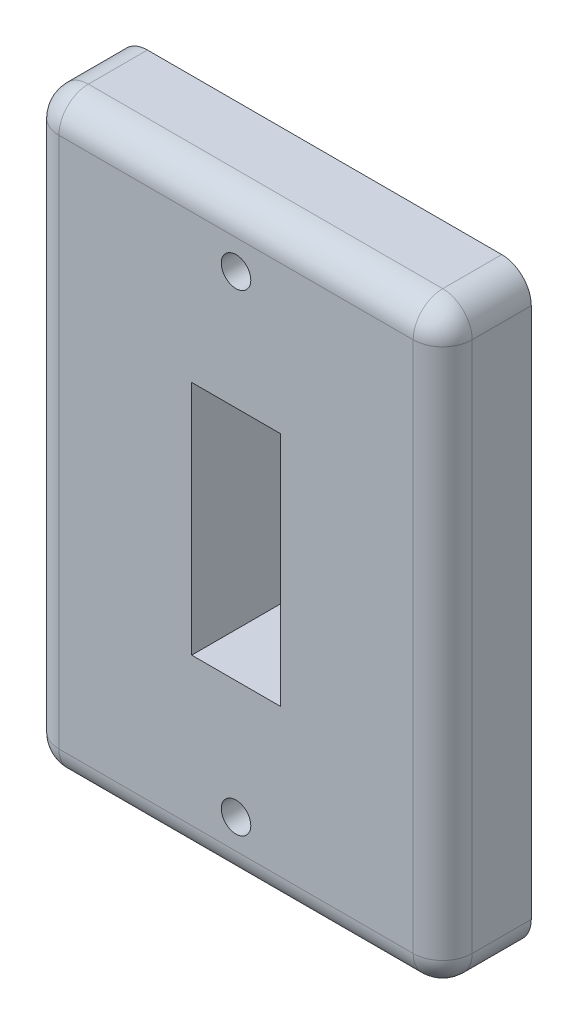
SolidWorks part; units mm, degrees
ref_plane "Front Plane" through (0, 0, 0) normal (0, 0, 1) x (1, 0, 0)
ref_plane "Top Plane" through (0, 0, 0) normal (0, 1, 0) x (1, 0, 0)
ref_plane "Right Plane" through (0, 0, 0) normal (1, 0, 0) x (0, 0, -1)
sketch "Sketch1" plane through (0, 0, 0) normal (0, 0, 1) x (1, 0, 0)
  line L1 (-35, -50) -> (35, -50)
  line L2 (-35, -50) -> (-35, 50)
  line L3 (-35, 50) -> (35, 50)
  line L4 (35, -50) -> (35, 50)
  line L5 (-35, -50) -> (35, 50) construction
  line L6 (-35, 50) -> (35, -50) construction
  point P0 (0, 0)
extrude "Boss-Extrude1" add sketch "Sketch1" along normal blind 15
sketch "Sketch3" plane through (0, 0, 15) normal (0, 0, 1) x (1, 0, 0)
  line L1 (-7.5, -20) -> (7.5, -20)
  line L2 (-7.5, -20) -> (-7.5, 20)
  line L3 (-7.5, 20) -> (7.5, 20)
  line L4 (7.5, -20) -> (7.5, 20)
  line L5 (-7.5, -20) -> (7.5, 20) construction
  line L6 (-7.5, 20) -> (7.5, -20) construction
  point P0 (0, 0)
extrude "Cut-Extrude1" cut sketch "Sketch3" against normal through all
sketch "Sketch4" plane through (0, 0, 15) normal (0, 0, 1) x (1, 0, 0)
  line L0 (0, 0) -> (0, -50) construction
  line L1 (-35, -50) -> (35, -50) construction
  line L2 (0, -50) -> (0, 50) construction
  line L3 (35, 50) -> (-35, 50) construction
  line L4 (0, 50) -> (0, 40) construction
  line L5 (0, -50) -> (0, -40) construction
  circle A0 centre (0, -40) radius 2.5
  circle A1 centre (0, 40) radius 2.5
extrude "Cut-Extrude2" cut sketch "Sketch4" against normal through all
fillet "Fillet1" radius 5 4 edges at (0, -50, 15) (35, 0, 15) (0, 50, 15) (-35, 0, 15)
sketch "Sketch5" plane through (0, 0, 0) normal (0, 0, -1) x (-1, 0, 0)
  circle A0 centre (0, 40) radius 1
  circle A1 centre (0, 40) radius 2.5
  circle A2 centre (0, -40) radius 1
  circle A3 centre (0, -40) radius 2.5
extrude "Boss-Extrude2" add sketch "Sketch5" against normal blind 2
fillet "Fillet2" radius 5 8 edges at (33.5355, -48.5355, 13.5355) (-33.5355, -48.5355, 13.5355) (-33.5355, 48.5355, 13.5355) (33.5355, 48.5355, 13.5355) (35, -50, 5) (-35, -50, 5) (-35, 50, 5) (35, 50, 5)
